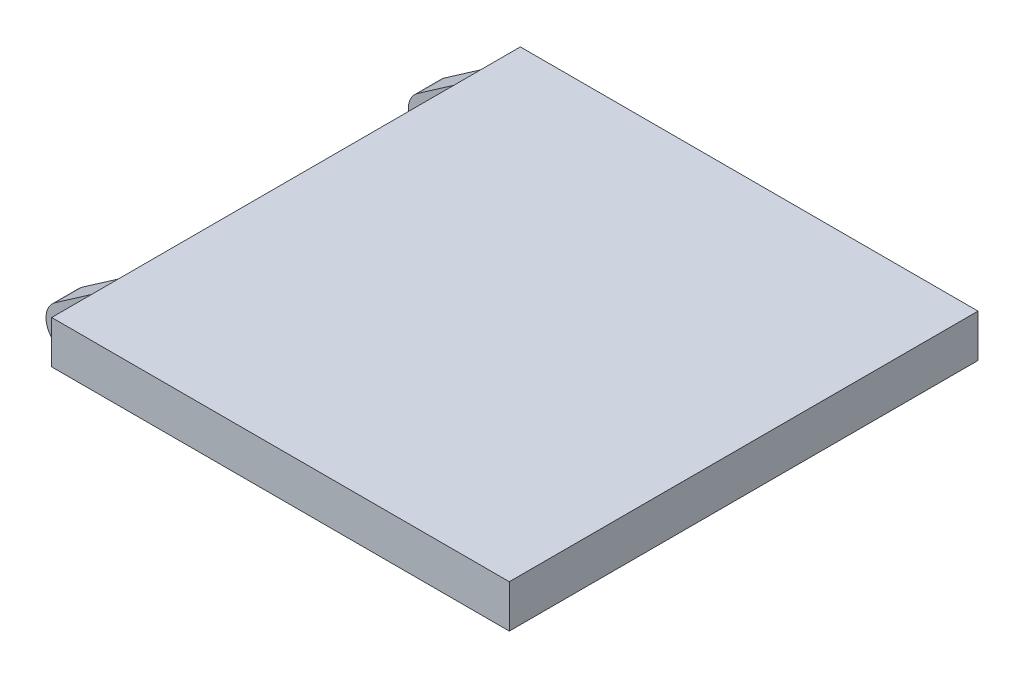
SolidWorks part; units mm, degrees
ref_plane "Front Plane" through (0, 0, 0) normal (0, 0, 1) x (1, 0, 0)
ref_plane "Top Plane" through (0, 0, 0) normal (0, 1, 0) x (1, 0, 0)
ref_plane "Right Plane" through (0, 0, 0) normal (1, 0, 0) x (0, 0, -1)
sketch "Sketch1" plane through (0, 0, 0) normal (0, 1, 0) x (1, 0, 0)
  line L1 (42.7791, -43.812) -> (-42.7791, -43.812)
  line L2 (42.7791, -43.812) -> (42.7791, 43.812)
  line L3 (42.7791, 43.812) -> (-42.7791, 43.812)
  line L4 (-42.7791, -43.812) -> (-42.7791, 43.812)
  line L5 (42.7791, -43.812) -> (-42.7791, 43.812) construction
  line L6 (42.7791, 43.812) -> (-42.7791, -43.812) construction
  point P0 (0, 0)
extrude "Boss-Extrude1" add sketch "Sketch1" along normal blind 8
sketch "Sketch2" plane through (0, 0, 36.97) normal (0, 0, -1) x (-1, 0, 0)
  line L2 (42.7791, 0) -> (42.7791, 8)
  line L3 (42.7791, 0) -> (43.2791, 0)
  line L4 (42.7791, 8) -> (49.5623, 3.2843)
  arc A1 (44.9959, 3.2843) -> (51.2791, 0) centre (47.2791, 0) ccw construction
  arc A2 (43.2791, 0) -> (49.5623, 3.2843) centre (47.2791, 0) ccw
extrude "Boss-Extrude2" add sketch "Sketch2" along normal blind 5 from offset 0.6 separate body
sketch "Sketch3" plane through (0, 0, 36.97) normal (0, 0, -1) x (-1, 0, 0)
  circle A0 centre (47.2791, 0) radius 2
  arc A1 (43.2791, 0) -> (49.5623, 3.2843) centre (47.2791, 0) ccw construction
  point P3 (53.4578, 12.6474)
  dimension "D1" = 4
extrude "Boss-Extrude3" add sketch "Sketch3" along normal blind 3.8 draft 14 separate body
fillet "Fillet1" radius 1 1 edges at (-48.3317, 0, 33.17)
combine bodies "Combine1" operation type subtract main body 102 bodies to subtract 103
surface "reduce to 0.1 if too loose" parameters "D1"=0.4
ref_plane "Plane1" through (0, 0, 0) normal (0, 0, -1) x (-1, 0, 0)
mirror "Mirror1" about plane through (0, 0, 0) normal (0, 0, -1) of bodies 104
